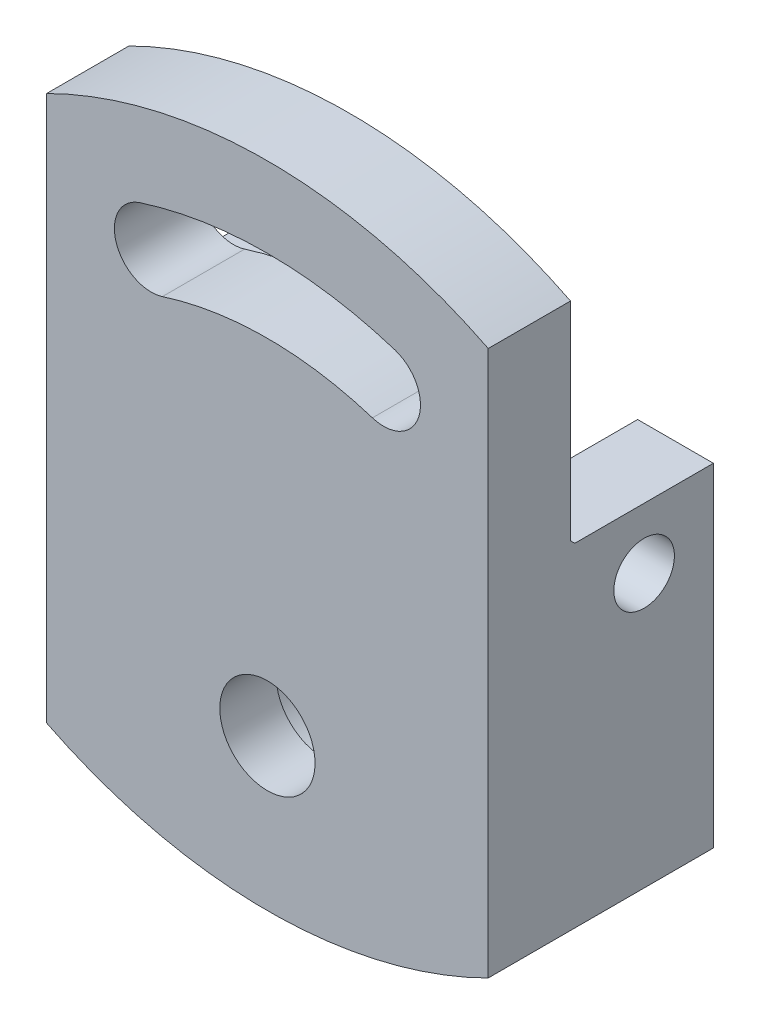
SolidWorks part; units mm, degrees
ref_plane "Ön Düzlem" through (0, 0, 0) normal (0, 0, 1) x (1, 0, 0)
ref_plane "Üst Düzlem" through (0, 0, 0) normal (0, 1, 0) x (1, 0, 0)
ref_plane "Sağ Düzlem" through (0, 0, 0) normal (1, 0, 0) x (0, 0, -1)
sketch "Çizim2" plane through (0, 0, 0) normal (0, 0, 1) x (1, 0, 0)
  line L0 (0, 0) -> (0, 150) construction
  line L2 (-51, 12.0441) -> (-51, 137.9559)
  line L4 (51, 137.9559) -> (51, 12.0441)
  arc A0 (-51, 137.9559) -> (51, 137.9559) centre (0, 36) cw
  arc A1 (-51, 12.0441) -> (51, 12.0441) centre (0, 114) ccw
  dimension "D2" = 114
  dimension "D1" = 150
  dimension "D3" = 102
extrude "Yükseklik-Ekstrüzyon1" add sketch "Çizim2" along normal mid plane 20
sketch "Çizim3" plane through (0, 0, 0) normal (1, 0, 0) x (0, 0, -1)
  line L0 (10, 150) -> (9, 150)
  line L1 (10, 150) -> (-10, 150) construction
  line L2 (9, 150) -> (9, 89)
  line L3 (9, 89) -> (10, 89)
  line L4 (10, 12.0441) -> (10, 137.9559) construction
  line L5 (10, 89) -> (10, 150)
  line L6 (-10, 0) -> (10, 0) construction
  dimension "D1" = 1
  dimension "D2" = 89
extrude "Kes-Ekstrüzyon1" cut sketch "Çizim3" against normal through all and the other way through all
chamfer "Pah1" distance 1 angle 45 1 edges at (0, 89, -9)
sketch "Çizim4" plane through (0, 0, 0) normal (1, 0, 0) x (0, 0, -1)
  line L0 (10, 89) -> (42, 89)
  line L1 (42, 89) -> (42, 0)
  line L2 (42, 0) -> (10, 0)
  line L3 (-10, 0) -> (10, 0) construction
  line L4 (10, 0) -> (10, 89)
  dimension "D1" = 32
extrude "Yükseklik-Ekstrüzyon2" add sketch "Çizim4" along direction (-1, 0, 0) on the side of the normal up to surface (51 mm away) and the other way up to surface (51 mm away) up to face at (51, 79.8333, -3) other way up to face at (-51, 79.8333, -3)
sketch "Çizim7" plane through (0, 0, -10) normal (0, 0, 1) x (1, 0, 0)
  line L0 (-51, 12.0441) -> (-51, 0) construction
  line L1 (-51, 0) -> (0, 0) construction
  line L2 (0, 0) -> (51, 0) construction
  line L3 (51, 0) -> (51, 12.0441) construction
  line L4 (-51, 12.0441) -> (-51, 0)
  line L5 (-51, 0) -> (0, 0)
  line L6 (0, 0) -> (51, 0)
  line L7 (51, 0) -> (51, 12.0441)
  arc A0 (-51, 12.0441) -> (0, 0) centre (0, 114) ccw construction
  arc A1 (0, 0) -> (51, 12.0441) centre (0, 114) ccw construction
  arc A2 (-51, 12.0441) -> (0, 0) centre (0, 114) ccw
  arc A3 (0, 0) -> (51, 12.0441) centre (0, 114) ccw
  arc M1 (0, 0) -> (-51, 12.0441) centre (0, 114) cw
  line M2 (-51, 12.0441) -> (-51, 0)
  line M3 (-51, 0) -> (0, 0)
extrude "Kes-Ekstrüzyon2" cut sketch "Çizim7" against normal through all contours M3 M1 M2 | A3 L6 L7 region at (-38.3886, 3.578, -10) region at (38.3886, 3.578, -10)
sketch "Çizim8" plane through (0, 0, 0) normal (1, 0, 0) x (0, 0, -1)
  line L0 (10, 89) -> (42, 89)
  line L1 (42, 89) -> (42, 0)
  line L2 (-10, 0) -> (42, 0) construction
  line L3 (42, 0) -> (42, 12.0441) construction
  line L4 (42, 0) -> (10, 0)
  line L5 (10, 0) -> (10, 89)
extrude "Kes-Ekstrüzyon3" cut sketch "Çizim8" against normal mid plane 67
sketch "Çizim9" plane through (0, 0, 0) normal (1, 0, 0) x (0, 0, -1)
  line L0 (10, 89) -> (42, 89) construction
  line L1 (42, 89) -> (42, 12.0441) construction
  circle A0 centre (26, 75) radius 7
  dimension "D3" = 14
  dimension "D1" = 14
  dimension "D2" = 16
extrude "Kes-Ekstrüzyon4" cut sketch "Çizim9" against normal through all and the other way through all
sketch "Çizim10" plane through (0, 0, 0) normal (1, 0, 0) x (0, 0, -1)
  line L0 (-10, 35) -> (23.147, 35) construction
  line L1 (-10, 12.0441) -> (-10, 137.9559) construction
  line L2 (-10, 35) -> (-10, 46)
  line L3 (-10, 46) -> (3, 46)
  line L4 (3, 46) -> (3, 50)
  line L5 (3, 50) -> (10, 50)
  line L6 (10, 50) -> (10, 35)
  line L7 (-10, 0) -> (10, 0) construction
  line L9 (-10, 35) -> (10, 35)
  point P11 (-10, 40.5)
  dimension "D1" = 35
  dimension "D2" = 11
  dimension "D3" = 15
  dimension "D4" = 13
  dimension "D5" = 20
revolve "Kes-Döndür1" cut sketch "Çizim10" angle 360 about L0
sketch "Çizim11" plane through (0, 0, 0) normal (0, 0, 1) x (1, 0, 0)
  line L0 (0, 35) -> (0, 163.3412) construction
  arc A3 (26.8441, 118.8057) -> (-26.8441, 118.8057) centre (0, 35) ccw construction
  arc A4 (29.437, 126.9006) -> (-29.437, 126.9006) centre (0, 35) ccw
  arc A5 (24.2512, 110.7108) -> (-24.2512, 110.7108) centre (0, 35) ccw
  arc A6 (24.2512, 110.7108) -> (29.437, 126.9006) centre (26.8441, 118.8057) ccw
  arc A7 (-29.437, 126.9006) -> (-24.2512, 110.7108) centre (-26.8441, 118.8057) ccw
  point P4 (0, 123)
  dimension "D1" = 8.5
  dimension "D2" = 88
extrude "Kes-Ekstrüzyon5" cut sketch "Çizim11" along normal through all and the other way through all
